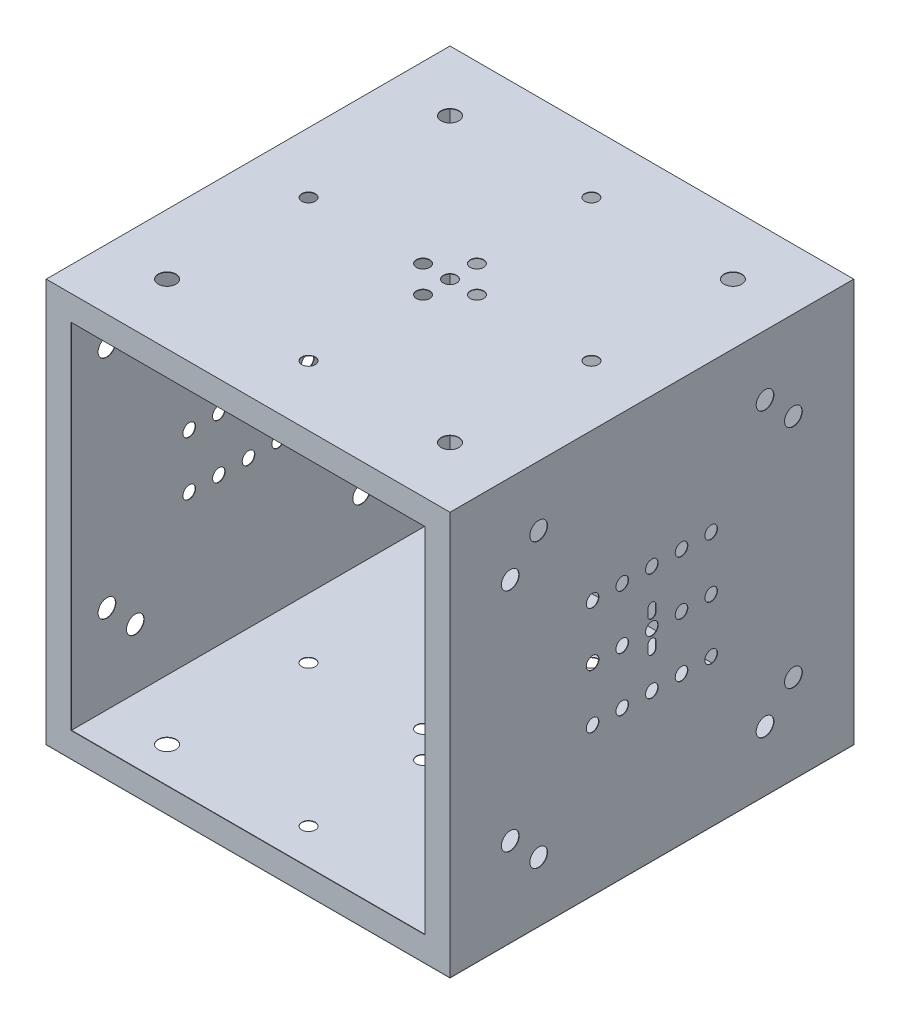
SolidWorks part; units mm, degrees
ref_plane "Front" through (0, 0, 0) normal (0, 0, 1) x (1, 0, 0)
ref_plane "Top" through (0, 0, 0) normal (0, 1, 0) x (1, 0, 0)
ref_plane "Right" through (0, 0, 0) normal (1, 0, 0) x (0, 0, -1)
sketch "Sketch1" plane through (0, 0, 0) normal (0, 0, 1) x (1, 0, 0)
  line L1 (-1498.5, 1497) -> (1498.5, 1497)
  line L2 (-1498.5, 1497) -> (-1498.5, -1497)
  line L3 (-1498.5, -1497) -> (1498.5, -1497)
  line L4 (1498.5, 1497) -> (1498.5, -1497)
  line L5 (-1498.5, 1497) -> (1498.5, -1497) construction
  line L6 (-1498.5, -1497) -> (1498.5, 1497) construction
  point P0 (0, 0)
  dimension "D1" = 2997
  dimension "D2" = 2994
extrude "Boss-Extrude1" add sketch "Sketch1" along normal blind 2997
shell "Shell1" thickness 3 removed face at (0, 0, 2997)
sketch "Sketch2" plane through (0, 0, 2997) normal (0, 0, 1) x (1, 0, 0)
  line L1 (-1498.5, 1497) -> (1498.5, 1497)
  line L2 (-1498.5, 1497) -> (-1498.5, -1497)
  line L3 (-1498.5, -1497) -> (1498.5, -1497)
  line L4 (1498.5, 1497) -> (1498.5, -1497)
  line L5 (-1498.5, 1497) -> (1498.5, -1497) construction
  line L6 (-1498.5, -1497) -> (1498.5, 1497) construction
  line L7 (-1313.3146, 1312) -> (1313.3146, 1312)
  line L8 (-1313.3146, 1312) -> (-1313.3146, -1312)
  line L9 (-1313.3146, -1312) -> (1313.3146, -1312)
  line L10 (1313.3146, 1312) -> (1313.3146, -1312)
  line L11 (-1313.3146, 1312) -> (1313.3146, -1312) construction
  line L12 (-1313.3146, -1312) -> (1313.3146, 1312) construction
  point P0 (0, 0)
  point P7 (0, 0)
  dimension "D1" = 185
extrude "Boss-Extrude2" add sketch "Sketch2" against normal blind 3
sketch "Sketch3" plane through (-1498.5, 0, 0) normal (-1, 0, 0) x (0, 0, 1)
  line L0 (0, 0) -> (2997, 0) construction
  line L1 (2997, 1497) -> (2997, -1497) construction
  line L2 (1498.5, 1497) -> (1498.5, -1497) construction
  line L3 (2997, 1497) -> (0, 1497) construction
  line L4 (2997, -1497) -> (0, -1497) construction
  line L5 (1498.5, 0) -> (0, 1497) construction
  line L6 (1498.5, 92.5) -> (1498.5, 140) construction
  line L7 (1468.5, 92.5) -> (1468.5, 140)
  line L8 (1528.5, 92.5) -> (1528.5, 140)
  line L9 (1498.5, 0) -> (1278.5, 0) construction
  line L10 (1058.5, 0) -> (1058.5, 400) construction
  line L11 (1498.5, -92.5) -> (1498.5, -140) construction
  line L12 (1468.5, -92.5) -> (1468.5, -140)
  line L13 (1528.5, -92.5) -> (1528.5, -140)
  circle A0 centre (1498.5, 0) radius 46.75
  arc A1 (1468.5, 92.5) -> (1528.5, 92.5) centre (1498.5, 92.5) ccw
  arc A2 (1528.5, 140) -> (1468.5, 140) centre (1498.5, 140) ccw
  circle A3 centre (1278.5, 0) radius 46.75
  circle A4 centre (1058.5, 0) radius 46.75
  circle A5 centre (1058.5, 400) radius 46.75
  circle A6 centre (1278.5, 400) radius 46.75
  circle A7 centre (1498.5, 400) radius 46.75
  circle A8 centre (658.5, 1050) radius 65.8
  circle A9 centre (447.6593, 838.948) radius 65.8
  circle A10 centre (1718.5, 400) radius 46.75
  circle A11 centre (1718.5, 0) radius 46.75
  circle A12 centre (1938.5, 0) radius 46.75
  circle A13 centre (1938.5, 400) radius 46.75
  circle A14 centre (2549.3407, 838.948) radius 65.8
  circle A15 centre (2338.5, 1050) radius 65.8
  arc A16 (1468.5, -92.5) -> (1528.5, -92.5) centre (1498.5, -92.5) cw
  arc A17 (1528.5, -140) -> (1468.5, -140) centre (1498.5, -140) cw
  circle A18 centre (1058.5, -400) radius 46.75
  circle A19 centre (1278.5, -400) radius 46.75
  circle A20 centre (1498.5, -400) radius 46.75
  circle A21 centre (1718.5, -400) radius 46.75
  circle A22 centre (1938.5, -400) radius 46.75
  circle A23 centre (2549.3407, -838.948) radius 65.8
  circle A24 centre (2338.5, -1050) radius 65.8
  circle A25 centre (658.5, -1050) radius 65.8
  circle A26 centre (447.6593, -838.948) radius 65.8
  point P17 (1498.5, 116.25)
  point P54 (1498.5, -116.25)
  dimension "D1" = 93.5
  dimension "D2" = 30
  dimension "D9" = 131.6
  dimension "D3" = 92.5
  dimension "D4" = 47.5
  dimension "D6" = 220
  dimension "D8" = 400
  dimension "D10" = 1050
  dimension "D11" = 840
  dimension "D5" = 3
  dimension "D7" = 2
extrude "Cut-Extrude1" cut sketch "Sketch3" against normal through all
sketch "Sketch4" plane through (0, 1497, 0) normal (0, 1, 0) x (1, 0, 0)
  line L0 (0, 0) -> (0, -2997) construction
  line L1 (1498.5, -2997) -> (-1498.5, -2997) construction
  line L2 (-1498.5, -1498.5) -> (1498.5, -1498.5) construction
  line L3 (-1498.5, -2997) -> (-1498.5, 0) construction
  line L4 (1498.5, -2997) -> (1498.5, 0) construction
  line L5 (-1498.5, 0) -> (0, -1498.5) construction
  line L6 (0, -1498.5) -> (-200, -1498.5) construction
  line L7 (0, -1498.5) -> (-1050, -1498.5) construction
  circle A0 centre (0, -1498.5) radius 49.85
  circle A1 centre (-200, -1498.5) radius 49.85
  circle A2 centre (-1050, -1498.5) radius 49.85
  circle A3 centre (-1050, -448.5) radius 65.8
  circle A4 centre (200, -1498.5) radius 49.85
  circle A5 centre (1050, -1498.5) radius 49.85
  circle A6 centre (1050, -448.5) radius 65.8
  circle A7 centre (0, -2548.5) radius 49.85
  circle A8 centre (0, -1698.5) radius 49.85
  circle A9 centre (0, -1298.5) radius 49.85
  circle A10 centre (0, -448.5) radius 49.85
  circle A11 centre (1050, -2548.5) radius 65.8
  circle A12 centre (-1050, -2548.5) radius 65.8
  dimension "D1" = 99.7
  dimension "D5" = 131.6
  dimension "D2" = 200
  dimension "D4" = 1050
  dimension "D6" = 1050
  dimension "D3" = 2
  dimension "D7" = 2
extrude "Cut-Extrude2" cut sketch "Sketch4" against normal through all
sketch "Sketch5" plane through (0, 0, 0) normal (0, 0, -1) x (-1, 0, 0)
  line L0 (-1498.5, 0) -> (1498.5, 0) construction
  line L1 (-1498.5, -1497) -> (-1498.5, 1497) construction
  line L2 (1498.5, 1497) -> (1498.5, -1497) construction
  line L3 (0, 1497) -> (0, -1497) construction
  line L4 (-1498.5, 1497) -> (1498.5, 1497) construction
  line L5 (1498.5, -1497) -> (-1498.5, -1497) construction
  line L6 (0, 0) -> (-1498.5, 1497) construction
  circle A0 centre (0, 0) radius 91.2
  circle A1 centre (0, 140) radius 35.635
  circle A2 centre (-222, 382) radius 91.2
  circle A3 centre (222, -382) radius 91.2
  circle A4 centre (-900, 899.0991) radius 65.8
  circle A5 centre (0, -140) radius 35.635
  circle A6 centre (-900, -899.0991) radius 65.8
  circle A7 centre (900, -899.0991) radius 65.8
  circle A8 centre (900, 899.0991) radius 65.8
  dimension "D1" = 182.4
  dimension "D2" = 71.27
  dimension "D4" = 182.4
  dimension "D7" = 182.4
  dimension "D10" = 131.6
  dimension "D3" = 140
  dimension "D5" = 222
  dimension "D6" = 382
  dimension "D8" = 222
  dimension "D9" = 382
  dimension "D11" = 900
extrude "Cut-Extrude3" cut sketch "Sketch5" against normal through all
split "Split1" bodies to split 107 resulting bodies 108 109 split by face at (0, -1494, 1748.35)
